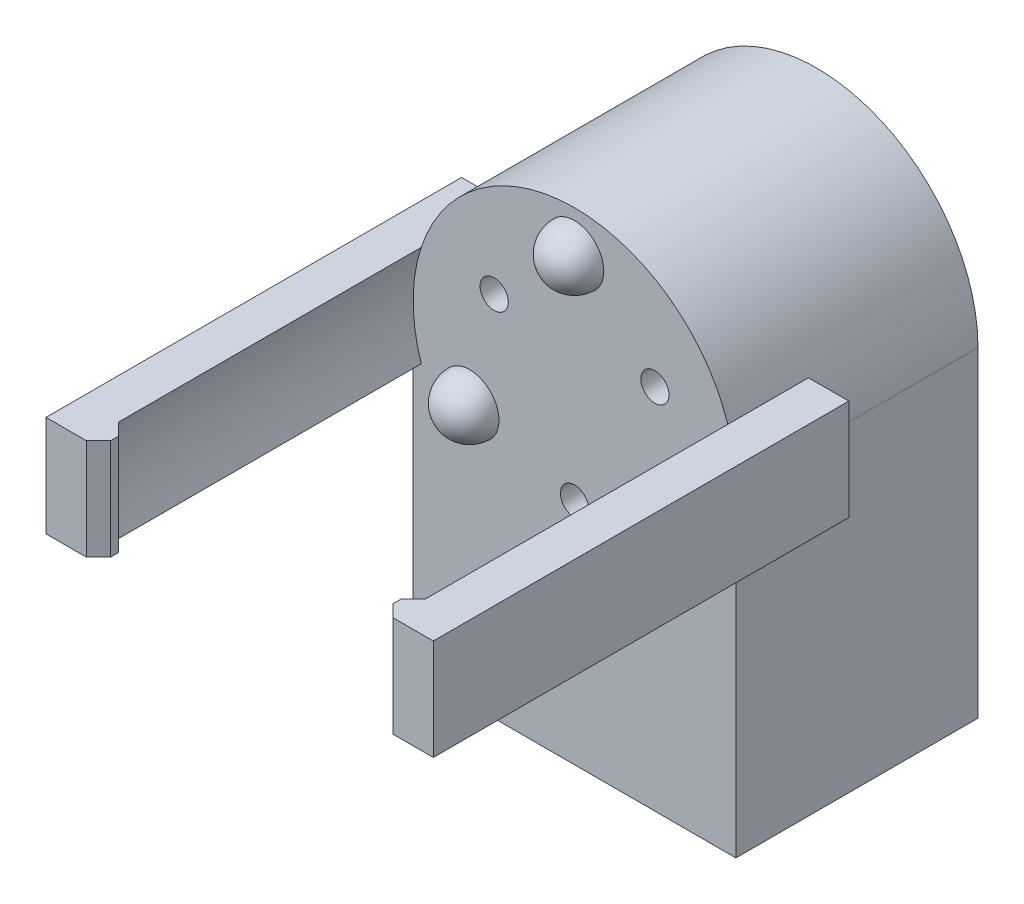
SolidWorks part; units mm, degrees
ref_plane "Front Plane" through (0, 0, 0) normal (0, 0, 1) x (1, 0, 0)
ref_plane "Top Plane" through (0, 0, 0) normal (0, 1, 0) x (1, 0, 0)
ref_plane "Right Plane" through (0, 0, 0) normal (1, 0, 0) x (0, 0, -1)
sketch "Sketch2" plane through (0, 0, 0) normal (0, 0, 1) x (1, 0, 0)
  circle A0 centre (0, 0) radius 4
  circle A1 centre (0, -2.3) radius 0.35
  circle A2 centre (-1.9919, 1.15) radius 0.35
  circle A3 centre (1.9919, 1.15) radius 0.35
  point P11 (0, 0)
  dimension "D1" = 8
  dimension "D2" = 0.7
  dimension "D3" = 2.3
  dimension "D4" = 3
extrude "Boss-Extrude1" add sketch "Sketch2" along normal blind 2
sketch "Sketch3" plane through (0, 0, 2) normal (0, 0, 1) x (1, 0, 0)
  circle A0 centre (0, 3) radius 0.725
  circle A1 centre (2.5981, -1.5) radius 0.725
  circle A2 centre (-2.5981, -1.5) radius 0.725
  point P9 (0, 0)
  dimension "D2" = 1.45
  dimension "D1" = 3
  dimension "D3" = 3
extrude "Boss-Extrude2" add sketch "Sketch3" along normal blind 0.725
fillet "Fillet1" radius 0.725 3 edges at (-1.8731, -1.5, 2.725) (3.3231, -1.5, 2.725) (0.725, 3, 2.725)
sketch "Sketch4" plane through (0, 0, 0) normal (0, 0, 1) x (1, 0, 0)
  line L0 (3.7997, 1.25) -> (4.7997, 1.25)
  line L1 (4.7997, 1.25) -> (4.7997, -1.25)
  line L2 (4.7997, -1.25) -> (3.7997, -1.25)
  line L3 (0, -55) -> (0, 55) construction
  line L4 (-4.7997, -1.25) -> (-3.7997, -1.25)
  line L5 (-4.7997, 1.25) -> (-4.7997, -1.25)
  line L6 (-3.7997, 1.25) -> (-4.7997, 1.25)
  circle A0 centre (0, 0) radius 4 construction
  arc A1 (3.7997, -1.25) -> (3.7997, 1.25) centre (0, 0) ccw
  arc A2 (-3.7997, -1.25) -> (-3.7997, 1.25) centre (0, 0) cw
  point P4 (4.7997, 0)
  dimension "D1" = 1
  dimension "D2" = 2.5
extrude "Boss-Extrude3" add sketch "Sketch4" along normal blind 9.5
sketch "Sketch5" plane through (0, -1.25, 0) normal (0, -1, 0) x (1, 0, 0)
  line L0 (3.7997, 9.5) -> (3.4997, 9.8)
  line L1 (3.4997, 9.8) -> (3.4997, 10)
  line L2 (3.4997, 10) -> (3.7997, 10.3)
  line L3 (3.7997, 10.3) -> (4.7997, 10.3)
  line L4 (4.7997, 10.3) -> (4.7997, 9.5)
  line L5 (3.7997, 9.5) -> (4.7997, 9.5) construction
  line L6 (3.7997, 9.5) -> (4.7997, 9.5)
  line L7 (0, -55) -> (0, 55) construction
  line L8 (-3.7997, 9.5) -> (-3.4997, 9.8)
  line L9 (-3.4997, 9.8) -> (-3.4997, 10)
  line L10 (-3.4997, 10) -> (-3.7997, 10.3)
  line L11 (-3.7997, 10.3) -> (-4.7997, 10.3)
  line L12 (-4.7997, 10.3) -> (-4.7997, 9.5)
  line L13 (-3.7997, 9.5) -> (-4.7997, 9.5)
  dimension "D1" = 0.3
  dimension "D2" = 0.2
extrude "Boss-Extrude4" add sketch "Sketch5" against normal blind 2.5
sketch "Sketch6" plane through (0, 0, 0) normal (0, 0, -1) x (-1, 0, 0)
  line L0 (-4, 0) -> (4, 0) construction
  line L1 (-4, -1.25) -> (-4, -7.9561)
  line L2 (-3.7997, -1.25) -> (-4.7997, -1.25) construction
  line L3 (-4, -7.9561) -> (4, -7.9561)
  line L4 (4, -1.25) -> (4, -7.9561)
  line L5 (4.7997, -1.25) -> (3.7997, -1.25) construction
  line L6 (-3.7997, -1.25) -> (-4, -1.25)
  line L7 (3.7997, -1.25) -> (4, -1.25)
  arc A0 (-3.7997, -1.25) -> (3.7997, -1.25) centre (0, 0) ccw construction
  arc A1 (-3.7997, -1.25) -> (3.7997, -1.25) centre (0, 0) ccw
  point P5 (0, 0)
  dimension "D1" = 8
extrude "Boss-Extrude5" add sketch "Sketch6" against normal blind 2
sketch "Sketch7" plane through (0, 0, 0) normal (0, 0, -1) x (-1, 0, 0)
  line L0 (-4, -7.9561) -> (4, -7.9561) construction
  line L1 (-4, -7.9561) -> (4, -7.9561)
  line L2 (-4, -7.9561) -> (-4, 0)
  line L3 (4, -7.9561) -> (4, 0)
  line L4 (-3.4, -7.3561) -> (3.4, -7.3561)
  line L5 (3.4, -7.3561) -> (3.4, 0)
  line L6 (-3.4, -7.3561) -> (-3.4, 0)
  arc A0 (4, 0) -> (-4, 0) centre (0, 0) ccw
  arc A1 (3.7997, 1.25) -> (-3.7997, 1.25) centre (0, 0) ccw construction
  arc A2 (3.4, 0) -> (-3.4, 0) centre (0, 0) ccw
  dimension "D1" = 0.6
extrude "Boss-Extrude6" add sketch "Sketch7" along normal blind 4
